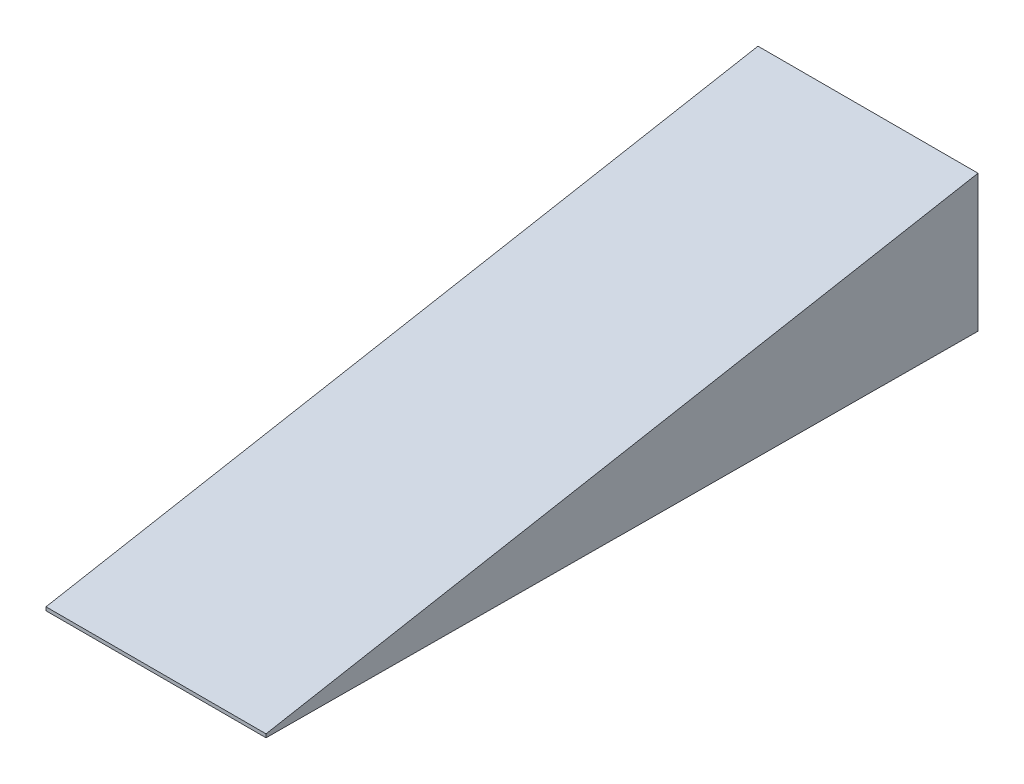
SolidWorks part; units mm, degrees
material "1.3# EPP"
ref_plane "Front Plane" through (0, 0, 0) normal (0, 0, 1) x (1, 0, 0)
ref_plane "Top Plane" through (0, 0, 0) normal (0, 1, 0) x (1, 0, 0)
ref_plane "Right Plane" through (0, 0, 0) normal (1, 0, 0) x (0, 0, -1)
sketch "Sketch1" plane through (0, 0, 0) normal (0, 0, 1) x (1, 0, 0)
  line L0 (16.3068, 8.6995) -> (-16.3068, 8.6995) construction
  line L1 (20.1168, 12.5095) -> (-20.1168, 12.5095)
  line L2 (20.1168, 12.5095) -> (20.1168, -12.5095)
  line L3 (20.1168, -12.5095) -> (-20.1168, -12.5095)
  line L4 (-20.1168, 12.5095) -> (-20.1168, -12.5095)
  line L5 (20.1168, 12.5095) -> (-20.1168, -12.5095) construction
  line L6 (20.1168, -12.5095) -> (-20.1168, 12.5095) construction
  line L7 (-16.3068, 8.6995) -> (-16.3068, -8.6995) construction
  line L8 (16.3068, -8.6995) -> (-16.3068, -8.6995) construction
  line L9 (16.3068, 8.6995) -> (16.3068, -8.6995) construction
  point P0 (0, 0)
  dimension "D1" = 25.019
  dimension "D2" = 40.2336
  dimension "D3" = 3.81
sketch3d "3DSketch1"
  line L1 (0, -6.8008, 130.175) -> (0, 49993.1992, 130.175) construction
  line L2 (0, 0, 130.175) -> (-50000, 0, 130.175) construction
  line L5 (-20.1168, -11.811, 130.175) -> (20.1168, -11.811, 130.175)
  line L6 (-20.1168, -11.811, 130.175) -> (-20.1168, -11.176, 130.175)
  line L7 (-20.1168, -11.176, 130.175) -> (20.1168, -11.176, 130.175)
  line L8 (20.1168, -11.811, 130.175) -> (20.1168, -11.176, 130.175)
  point P1 (0, -11.176, 130.175)
  dimension "D1" = 130.175
  dimension "D2" = 40.2336
  dimension "D3" = 0.635
  dimension "D4" = 11.176
loft "Loft1" add profiles "Sketch1", "3DSketch1" connector at (-20.1168, -12.5095, 0) connector at (-20.1168, -11.811, 130.175)
shell "Shell1" thickness 3.175 removed face at (0, 0, 0)
